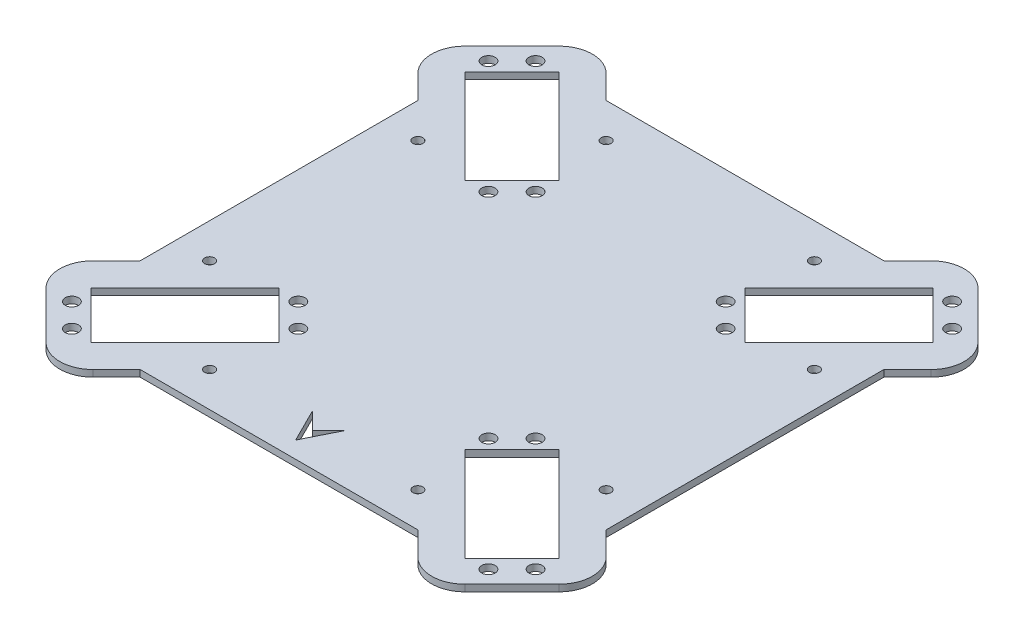
SolidWorks part; units mm, degrees
ref_plane "Front Plane" through (0, 0, 0) normal (0, 0, 1) x (1, 0, 0)
ref_plane "Top Plane" through (0, 0, 0) normal (0, 1, 0) x (1, 0, 0)
ref_plane "Right Plane" through (0, 0, 0) normal (1, 0, 0) x (0, 0, -1)
sketch "Sketch1" plane through (0, 0, 0) normal (0, 1, 0) x (1, 0, 0)
  line L1 (0, 0) -> (140, 0)
  line L2 (0, 0) -> (0, 140)
  line L3 (0, 140) -> (140, 140)
  line L4 (140, 0) -> (140, 140)
  dimension "D1" = 140
  dimension "D2" = 140
extrude "Boss-Extrude1" add sketch "Sketch1" along normal blind 2
sketch "Sketch2" plane through (0, 2, 0) normal (0, 1, 0) x (1, 0, 0)
  line L0 (70, 140) -> (70, 0) construction
  line L1 (140, 140) -> (0, 140) construction
  line L2 (0, 0) -> (140, 0) construction
  line L3 (140, 70) -> (0, 70) construction
  line L4 (140, 0) -> (140, 140) construction
  line L5 (0, 140) -> (0, 0) construction
  line L6 (70, 70) -> (140, 140) construction
  line L7 (125.8579, 125.8579) -> (140, 111.7157) construction
  line L8 (125.8579, 125.8579) -> (111.7157, 140) construction
  line L9 (111.7157, 140) -> (140, 111.7157)
  line L10 (111.7157, 140) -> (125.8579, 154.1421)
  line L11 (140, 111.7157) -> (154.1421, 125.8579)
  line L12 (125.8579, 154.1421) -> (154.1421, 125.8579)
  line L13 (0, 111.7157) -> (-14.1421, 125.8579)
  line L14 (14.1421, 154.1421) -> (-14.1421, 125.8579)
  line L15 (28.2843, 140) -> (14.1421, 154.1421)
  line L16 (28.2843, 140) -> (0, 111.7157)
  line L17 (28.2843, 0) -> (0, 28.2843)
  line L18 (28.2843, 0) -> (14.1421, -14.1421)
  line L19 (14.1421, -14.1421) -> (-14.1421, 14.1421)
  line L20 (0, 28.2843) -> (-14.1421, 14.1421)
  line L21 (140, 28.2843) -> (154.1421, 14.1421)
  line L22 (125.8579, -14.1421) -> (154.1421, 14.1421)
  line L23 (111.7157, 0) -> (125.8579, -14.1421)
  line L24 (111.7157, 0) -> (140, 28.2843)
  point P32 (0, 0)
  point P33 (140, 111.7157)
  point P34 (111.7157, 140)
  point P35 (0, 0)
  dimension "D1" = 40
  dimension "D2" = 20
extrude "Boss-Extrude3" add sketch "Sketch2" against normal blind 2
sketch "Sketch3" plane through (0, 2, 0) normal (0, 1, 0) x (1, 0, 0)
  line L0 (0, 0) -> (140, 140) construction
  line L1 (-14.1421, 14.1421) -> (14.1421, -14.1421) construction
  line L2 (154.1421, 125.8579) -> (125.8579, 154.1421) construction
  line L3 (0, 28.2843) -> (28.2843, 0) construction
  line L4 (6.7246, 6.7246) -> (20.8667, -7.4176) construction
  line L5 (14.1421, -14.1421) -> (28.2843, 0) construction
  line L6 (35.0089, 35.0089) -> (47.7718, 22.2459) construction
  line L7 (13.7957, -0.3465) -> (42.0799, 27.9378)
  line L8 (13.7957, -0.3465) -> (-0.3465, 13.7957)
  line L9 (42.0799, 27.9378) -> (27.9378, 42.0799)
  line L10 (-0.3465, 13.7957) -> (27.9378, 42.0799)
  line L11 (3.8891, 3.8891) -> (10.9525, -3.1743) construction
  line L12 (27.9696, 13.8275) -> (13.8275, 27.9696) construction
  line L13 (0, 70) -> (140, 70) construction
  line L14 (0, 111.7157) -> (0, 28.2843) construction
  line L15 (140, 28.2843) -> (140, 111.7157) construction
  line L16 (70, 0) -> (70, 140) construction
  line L17 (28.2843, 0) -> (111.7157, 0) construction
  line L18 (111.7157, 140) -> (28.2843, 140) construction
  line L19 (97.9201, 27.9378) -> (112.0622, 42.0799)
  line L20 (140.3465, 13.7957) -> (112.0622, 42.0799)
  line L21 (126.2043, -0.3465) -> (140.3465, 13.7957)
  line L22 (126.2043, -0.3465) -> (97.9201, 27.9378)
  line L23 (126.2043, 140.3465) -> (97.9201, 112.0622)
  line L24 (126.2043, 140.3465) -> (140.3465, 126.2043)
  line L25 (140.3465, 126.2043) -> (112.0622, 97.9201)
  line L26 (97.9201, 112.0622) -> (112.0622, 97.9201)
  line L27 (42.0799, 112.0622) -> (27.9378, 97.9201)
  line L28 (-0.3465, 126.2043) -> (27.9378, 97.9201)
  line L29 (13.7957, 140.3465) -> (-0.3465, 126.2043)
  line L30 (13.7957, 140.3465) -> (42.0799, 112.0622)
  circle A0 centre (7.4246, 0.3536) radius 2
  circle A1 centre (0.3536, 7.4246) radius 2
  circle A2 centre (41.4435, 34.3725) radius 2
  circle A3 centre (34.3725, 41.4435) radius 2
  circle A4 centre (132.5754, 0.3536) radius 2
  circle A5 centre (139.6464, 7.4246) radius 2
  circle A6 centre (98.5565, 34.3725) radius 2
  circle A7 centre (105.6275, 41.4435) radius 2
  circle A8 centre (132.5754, 139.6464) radius 2
  circle A9 centre (139.6464, 132.5754) radius 2
  circle A10 centre (98.5565, 105.6275) radius 2
  circle A11 centre (105.6275, 98.5565) radius 2
  circle A12 centre (7.4246, 139.6464) radius 2
  circle A13 centre (0.3536, 132.5754) radius 2
  circle A14 centre (41.4435, 105.6275) radius 2
  circle A15 centre (34.3725, 98.5565) radius 2
  point P10 (14.1421, 14.1421)
  point P11 (35.0089, 35.0089)
  point P13 (6.7246, 6.7246)
  point P83 (0, 0)
  point P84 (0, 0)
  dimension "D5" = 4
  dimension "D6" = 10
  dimension "D7" = 4.1
  dimension "D1" = 29.51
  dimension "D2" = 10.49
  dimension "D3" = 20
  dimension "D4" = 4.01
extrude "Cut-Extrude1" cut sketch "Sketch3" against normal blind 2
fillet "Fillet1" radius 10 8 edges at (154.1421, 1, -14.1421) (125.8579, 1, 14.1421) (14.1421, 1, 14.1421) (-14.1421, 1, -14.1421) (-14.1421, 1, -125.8579) (14.1421, 1, -154.1421) (125.8579, 1, -154.1421) (154.1421, 1, -125.8579)
sketch "Sketch4" plane through (0, 2, 0) normal (0, 1, 0) x (1, 0, 0)
  line L0 (70, 140) -> (70, 0) construction
  line L1 (111.7157, 140) -> (28.2843, 140) construction
  line L2 (28.2843, 0) -> (111.7157, 0) construction
  line L3 (0, 70) -> (140, 70) construction
  line L4 (0, 111.7157) -> (0, 28.2843) construction
  line L5 (140, 28.2843) -> (140, 111.7157) construction
  line L6 (28.2843, 0) -> (70, 41.7157) construction
  line L7 (35.0089, 35.0089) -> (6.7246, 6.7246) construction
  line L8 (42.0799, 27.9378) -> (27.9378, 42.0799) construction
  line L9 (-0.3465, 13.7957) -> (13.7957, -0.3465) construction
  line L10 (42.0799, 27.9378) -> (28.2843, 0) construction
  line L11 (35.1821, 13.9689) -> (38.7176, 10.4334) construction
  circle A0 centre (38.7176, 10.4334) radius 1.5
  circle A1 centre (10.4334, 38.7176) radius 1.5
  circle A2 centre (101.2824, 10.4334) radius 1.5
  circle A3 centre (129.5666, 38.7176) radius 1.5
  circle A4 centre (38.7176, 129.5666) radius 1.5
  circle A5 centre (10.4334, 101.2824) radius 1.5
  circle A6 centre (101.2824, 129.5666) radius 1.5
  circle A7 centre (129.5666, 101.2824) radius 1.5
  point P27 (0, 0)
  point P33 (0, 0)
  dimension "D1" = 3
extrude "Cut-Extrude2" cut sketch "Sketch4" against normal blind 2
sketch "Sketch5" plane through (0, 2, 0) normal (0, 1, 0) x (1, 0, 0)
  line L0 (70, 0) -> (70, 140) construction
  line L1 (28.2843, 0) -> (111.7157, 0) construction
  line L2 (111.7157, 140) -> (28.2843, 140) construction
  line L3 (70, 15) -> (75, 15) construction
  line L4 (75, 15) -> (70, 10)
  line L5 (75, 15) -> (70, 5)
  line L6 (65, 15) -> (70, 5)
  line L7 (65, 15) -> (70, 10)
  dimension "D1" = 5
  dimension "D2" = 5
  dimension "D3" = 10
  dimension "D4" = 5
extrude "Cut-Extrude3" cut sketch "Sketch5" against normal blind 2
